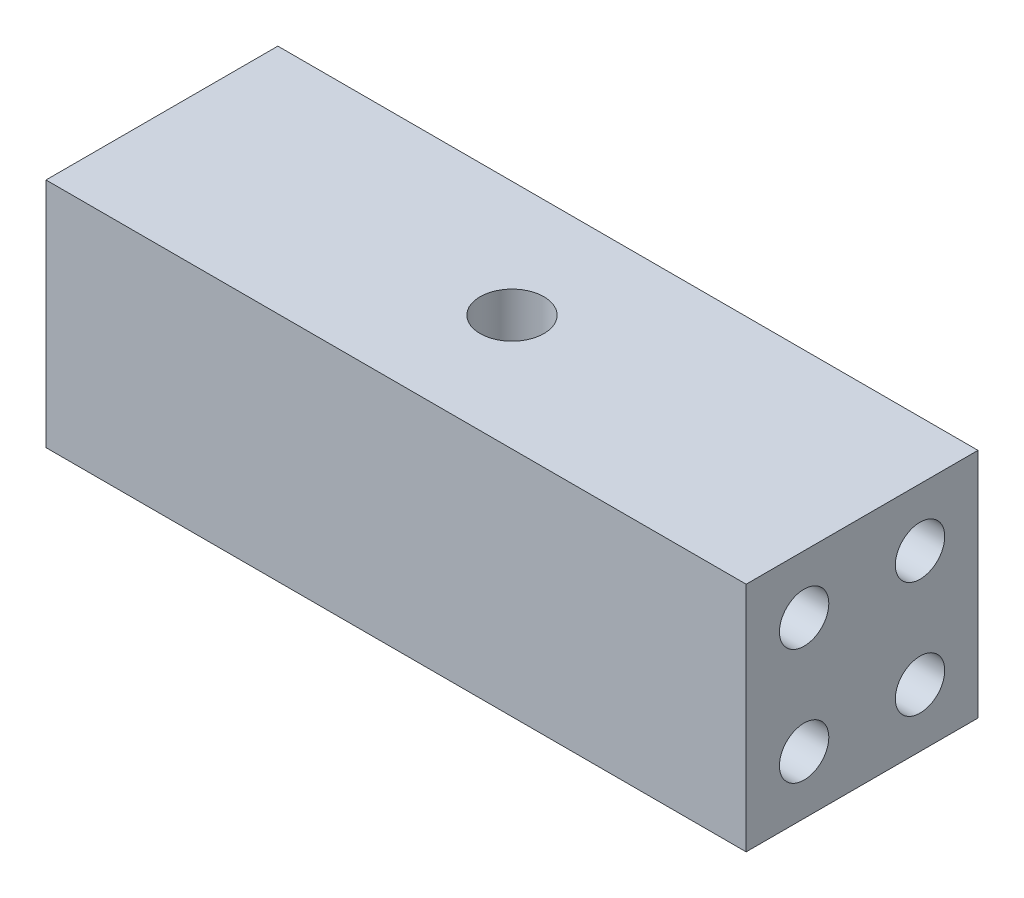
SolidWorks part; units mm, degrees
material "6061-T6 (SS)"
ref_plane "Front Plane" through (0, 0, 0) normal (0, 0, 1) x (1, 0, 0)
ref_plane "Top Plane" through (0, 0, 0) normal (0, 1, 0) x (1, 0, 0)
ref_plane "Right Plane" through (0, 0, 0) normal (1, 0, 0) x (0, 0, -1)
sketch "Sketch1" plane through (0, 0, 0) normal (0, 1, 0) x (1, 0, 0)
  line L1 (0, 0) -> (76.708, 0)
  line L2 (0, 0) -> (0, 25.4)
  line L3 (0, 25.4) -> (76.708, 25.4)
  line L4 (76.708, 0) -> (76.708, 25.4)
  dimension "D1" = 25.4
  dimension "D2" = 76.708
extrude "Boss-Extrude1" add sketch "Sketch1" along normal blind 25.4
hole_wizard "1/4-28 Tapped Hole1" positions "Sketch2" profile "Sketch3" tap size "1/4-28" standard "ANSI Inch"
sketch "Sketch2" plane through (76.708, 0, 0) normal (1, 0, 0) x (0, 0, -1)
  point P0 (6.35, 19.05)
  point P2 (19.05, 19.05)
  point P4 (19.05, 6.35)
  point P6 (6.35, 6.35)
  dimension "D1" = 6.35
  dimension "D2" = 6.35
  dimension "D3" = 6.35
  dimension "D4" = 6.35
  dimension "D5" = 6.35
  dimension "D6" = 6.35
  dimension "D7" = 6.35
  dimension "D8" = 6.35
sketch "Sketch3" plane through (76.708, 19.05, -6.35) normal (0, 1, 0) x (0, 0, -1)
  line L0 (0, 0) -> (0, 10.7694)
  line L1 (0, 10.7694) -> (2.7051, 9.144)
  line L2 (2.7051, 9.144) -> (2.7051, 0)
  line L5 (2.7051, 0) -> (0, 0)
  line L10 (0, 10.7694) -> (-2.7051, 9.144) construction
  line L11 (0, -6.35) -> (0, 107.95) construction
  dimension "Tap Drill Dia." = 5.4102
  dimension "Tap Drill Depth" = 9.144
  dimension "Drill Angle" = 118
cosmetic thread "Hole Thread1" parameters "D1"=6.35, "D2"=6.35
cosmetic thread "Hole Thread2" parameters "D1"=6.35, "D2"=6.35
cosmetic thread "Hole Thread3" parameters "D1"=6.35, "D2"=6.35
cosmetic thread "Hole Thread4" parameters "D1"=6.35, "D2"=6.35
hole_wizard "1/4-28 Tapped Hole2" positions "Sketch4" profile "Sketch5" tap size "1/4-28" standard "ANSI Inch"
sketch "Sketch4" plane through (0, 0, 0) normal (-1, 0, 0) x (0, 0, 1)
  point P0 (-19.05, 19.05)
  point P2 (-6.35, 19.05)
  point P4 (-6.35, 6.35)
  point P6 (-19.05, 6.35)
  dimension "D1" = 6.35
  dimension "D2" = 6.35
  dimension "D3" = 6.35
  dimension "D4" = 6.35
  dimension "D5" = 6.35
  dimension "D6" = 6.35
  dimension "D7" = 6.35
  dimension "D8" = 6.35
sketch "Sketch5" plane through (0, 19.05, -19.05) normal (0, 1, 0) x (0, 0, 1)
  line L0 (0, 0) -> (0, 10.7694)
  line L1 (0, 10.7694) -> (2.7051, 9.144)
  line L2 (2.7051, 9.144) -> (2.7051, 0)
  line L5 (2.7051, 0) -> (0, 0)
  line L10 (0, 10.7694) -> (-2.7051, 9.144) construction
  line L11 (0, -6.35) -> (0, 107.95) construction
  dimension "Tap Drill Dia." = 5.4102
  dimension "Tap Drill Depth" = 9.144
  dimension "Drill Angle" = 118
cosmetic thread "Hole Thread5" parameters "D1"=6.35, "D2"=6.35
cosmetic thread "Hole Thread6" parameters "D1"=6.35, "D2"=6.35
cosmetic thread "Hole Thread7" parameters "D1"=6.35, "D2"=6.35
cosmetic thread "Hole Thread8" parameters "D1"=6.35, "D2"=6.35
hole_wizard "Ø6.0mm Dowel Hole1" positions "Sketch7" profile "Sketch9" hole size "Ø6.0" standard "ANSI Metric" end condition through all
sketch "Sketch7" plane through (0, 25.4, 0) normal (0, 1, 0) x (1, 0, 0)
  point P0 (38.354, 12.7)
  dimension "D1" = 12.7
  dimension "D2" = 38.354
sketch "Sketch9" plane through (38.354, 25.4, -12.7) normal (1, 0, 0) x (0, 0, 1)
  line L0 (0, 0) -> (0, 25.4)
  line L1 (0, 25.4) -> (3.5, 25.4)
  line L2 (3.5, 25.4) -> (3.5, 0)
  line L5 (3.5, 0) -> (0, 0)
  line L11 (0, -6.35) -> (0, 107.95) construction
  dimension "Thru Hole Dia." = 7
  dimension "Thru Hole Depth" = 25.4
